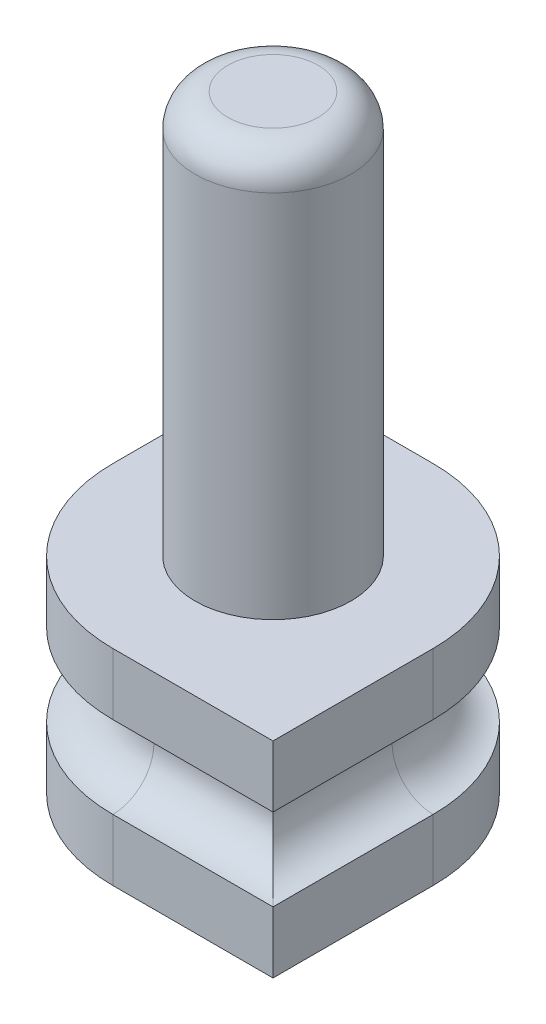
SolidWorks part; units mm, degrees
ref_plane "Front Plane" through (0, 0, 0) normal (0, 0, 1) x (1, 0, 0)
ref_plane "Top Plane" through (0, 0, 0) normal (0, 1, 0) x (1, 0, 0)
ref_plane "Right Plane" through (0, 0, 0) normal (1, 0, 0) x (0, 0, -1)
sketch "Sketch1" plane through (0, 0, 0) normal (0, 1, 0) x (1, 0, 0)
  line L1 (-3.9, 3.9) -> (0, 3.9)
  line L2 (-3.9, 3.9) -> (-3.9, 0)
  line L3 (0, -3.9) -> (3.9, -3.9)
  line L4 (3.9, 0) -> (3.9, -3.9)
  arc A0 (-3.9, 0) -> (0, -3.9) centre (0, 0) ccw
  arc A1 (3.9, 0) -> (0, 3.9) centre (0, 0) ccw
  point P0 (0, 0)
  dimension "D3" = 3.9
  dimension "D4" = 3.9
  dimension "D1" = 7.8
  dimension "D2" = 7.8
  dimension "D5" = 3.9
  dimension "D6" = 3.9
  dimension "D7" = 3.9
  dimension "D8" = 3.9
extrude "Boss-Extrude1" add sketch "Sketch1" along normal blind 5
sketch "Sketch2" plane through (0, 5, 0) normal (0, 1, 0) x (1, 0, 0)
  circle A0 centre (0, 0) radius 1.9
  dimension "D1" = 3.8
extrude "Boss-Extrude2" add sketch "Sketch2" along normal blind 9.8
ref_plane "Plane1" through (0, 2.5, 0) normal (0, 1, 0) x (1, 0, 0)
sketch "Sketch3" plane through (0, 2.5, 0) normal (0, 1, 0) x (1, 0, 0)
  line L0 (-3.9, 0) -> (-3.9, 3.9)
  line L1 (-3.9, 3.9) -> (0, 3.9)
  line L2 (3.9, 0) -> (3.9, -3.9)
  line L3 (3.9, -3.9) -> (0, -3.9)
  line L4 (-2.9, 0) -> (-2.9, 2.9)
  line L5 (-2.9, 2.9) -> (0, 2.9)
  line L6 (2.9, 0) -> (2.9, -2.9)
  line L7 (2.9, -2.9) -> (0, -2.9)
  arc A0 (-3.9, 0) -> (0, -3.9) centre (0, 0) ccw
  arc A1 (3.9, 0) -> (0, 3.9) centre (0, 0) ccw
  arc A2 (2.9, 0) -> (0, 2.9) centre (0, 0) ccw
  arc A3 (-2.9, 0) -> (0, -2.9) centre (0, 0) ccw
  dimension "D1" = 1
extrude "Cut-Extrude2" cut sketch "Sketch3" against normal blind 1 and the other way blind 1
fillet "Fillet1" radius 1 12 edges at (2.9, 3.5, 1.45) (2.0506, 3.5, -2.0506) (1.45, 3.5, 2.9) (-2.0506, 3.5, 2.0506) (2.9, 1.5, 1.45) (2.0506, 1.5, -2.0506) (-2.9, 1.5, -1.45) (1.45, 1.5, 2.9) (-1.45, 3.5, -2.9) (-2.9, 3.5, -1.45) (-1.45, 1.5, -2.9) (-2.0506, 1.5, 2.0506)
fillet "Fillet2" radius 0.8 1 edges at (0, 14.8, 1.9)
